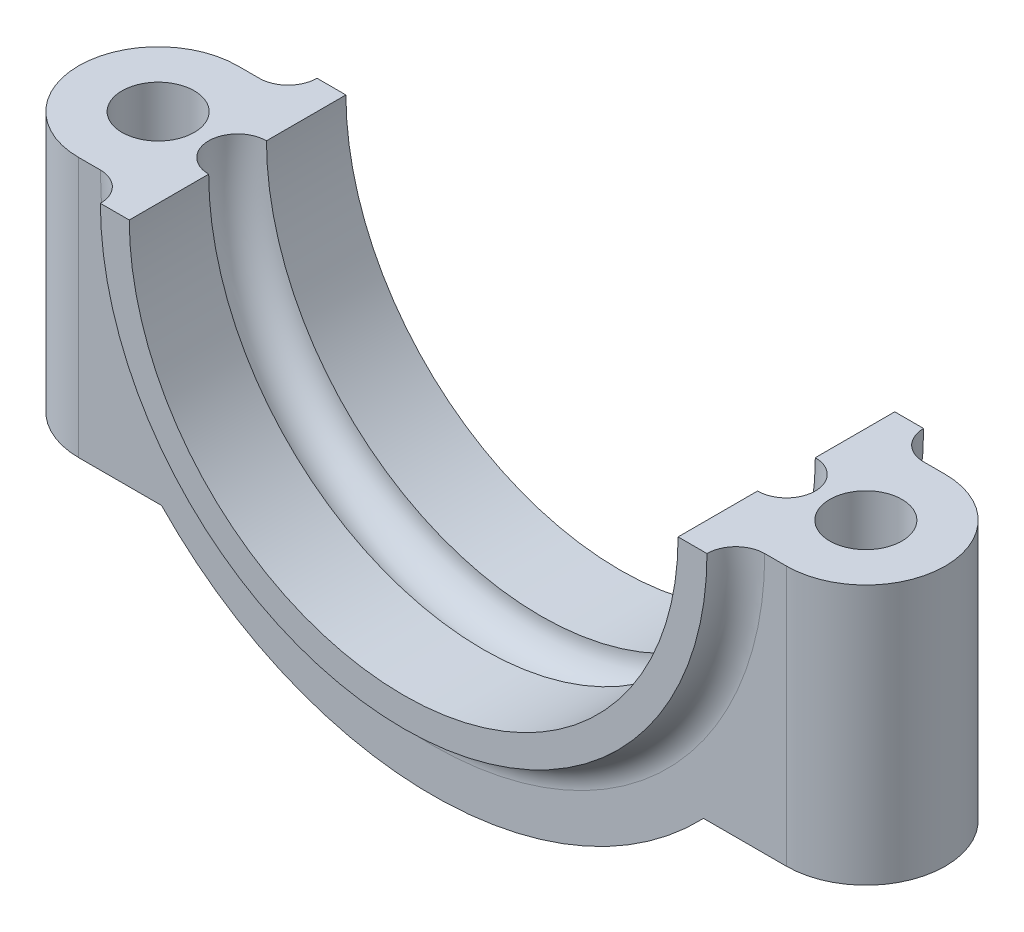
SolidWorks part; units mm, degrees
ref_plane "Front Plane" through (0, 0, 0) normal (0, 0, 1) x (1, 0, 0)
ref_plane "Top Plane" through (0, 0, 0) normal (0, 1, 0) x (1, 0, 0)
ref_plane "Right Plane" through (0, 0, 0) normal (1, 0, 0) x (0, 0, -1)
sketch "Sketch1" plane through (0, 0, 0) normal (0, 0, 1) x (1, 0, 0)
  line L0 (19, 0) -> (30, 0)
  line L1 (30, 0) -> (30, -18)
  line L2 (30, -18) -> (18.7617, -18)
  line L3 (0, 19) -> (0, 41.8915) construction
  line L4 (-30, -18) -> (-18.7617, -18)
  line L5 (-30, 0) -> (-30, -18)
  line L6 (-19, 0) -> (-30, 0)
  arc A0 (-19, 0) -> (19, 0) centre (0, 0) ccw
  arc A1 (-18.7617, -18) -> (18.7617, -18) centre (0, 0) ccw
  dimension "D1" = 38
  dimension "D2" = 52
  dimension "D3" = 60
  dimension "D4" = 18
extrude "Boss-Extrude1" add sketch "Sketch1" along normal mid plane 11
sketch "Sketch2" plane through (0, 0, 5.5) normal (0, 0, 1) x (1, 0, 0)
  line L0 (-21, 0) -> (-19, 0)
  line L1 (19, 0) -> (21, 0)
  arc A0 (-21, 0) -> (21, 0) centre (0, 0) ccw
  arc A1 (-19, 0) -> (19, 0) centre (0, 0) ccw construction
  arc A2 (-19, 0) -> (19, 0) centre (0, 0) ccw
  dimension "D1" = 42
extrude "Boss-Extrude2" add sketch "Sketch2" along normal blind 2 and the other way blind 13
sketch "Sketch3" plane through (0, 0, 0) normal (0, 1, 0) x (1, 0, 0)
  line L0 (30, -5.5) -> (19, 5.5) construction
  line L1 (19, -7.5) -> (19, 7.5) construction
  line L2 (30, -5.5) -> (30, 5.5) construction
  line L3 (0, 0) -> (0, 21.3747) construction
  circle A0 centre (24.5, 0) radius 2.5
  circle A1 centre (-24.5, 0) radius 2.5
  dimension "D2" = 5
  dimension "D1" = 45
extrude "Cut-Extrude1" cut sketch "Sketch3" against normal through all
sketch "Sketch4" plane through (0, 0, 0) normal (0, 1, 0) x (1, 0, 0)
  line L0 (19, -7.5) -> (19, 7.5) construction
  line L1 (0, 0) -> (0, 16.4738) construction
  circle A0 centre (19, 0) radius 2
  dimension "D1" = 4
revolve "Cut-Revolve1" cut sketch "Sketch4" angle 360 about L1
fillet "Fillet1" radius 2 2 edges at (0, -21, -5.5) (0, -21, 5.5)
fillet "Fillet2" 2 edges at (-30, -9, 5.5) (-30, -9, -5.5) type full round first side face at (0, -12.875, 5.5) second side face at (0, -12.875, -5.5) middle face at (-30, -9, 0)
fillet "Fillet3" 2 edges at (30, -9, -5.5) (30, -9, 5.5) type full round first side face at (1.375, -12.875, -5.5) second side face at (1.375, -12.875, 5.5) middle face at (30, -9, 0)
